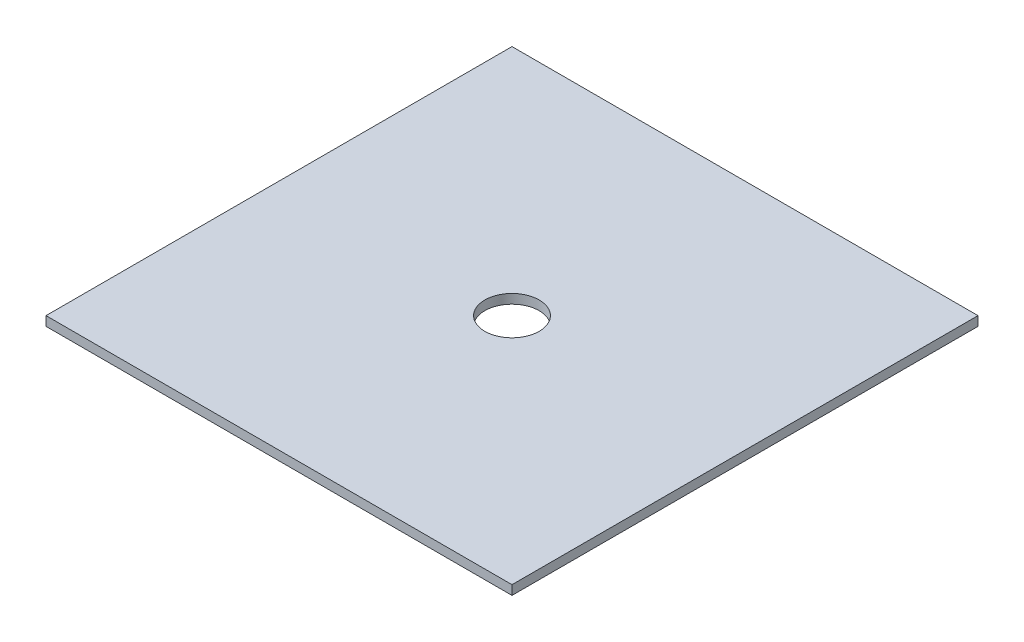
SolidWorks part; units mm, degrees
ref_plane "Plan de face" through (0, 0, 0) normal (0, 0, 1) x (1, 0, 0)
ref_plane "Plan de dessus" through (0, 0, 0) normal (0, 1, 0) x (1, 0, 0)
ref_plane "Plan de droite" through (0, 0, 0) normal (1, 0, 0) x (0, 0, -1)
sketch "Esquisse1" plane through (0, 0, 0) normal (0, 1, 0) x (1, 0, 0)
  line L1 (-150, -150) -> (150, -150)
  line L2 (-150, -150) -> (-150, 150)
  line L3 (-150, 150) -> (150, 150)
  line L4 (150, -150) -> (150, 150)
  line L5 (-150, -150) -> (150, 150) construction
  line L6 (-150, 150) -> (150, -150) construction
  point P0 (0, 0)
  dimension "D1" = 300
extrude "Boss.-Extru.1" add sketch "Esquisse1" along normal blind 6
sketch "Esquisse2" plane through (0, 6, 0) normal (0, 1, 0) x (1, 0, 0)
  circle A0 centre (0, 0) radius 17.5
  dimension "D1" = 35
extrude "Enlèv. mat.-Extru.1" cut sketch "Esquisse2" against normal through all both and the other way through all
